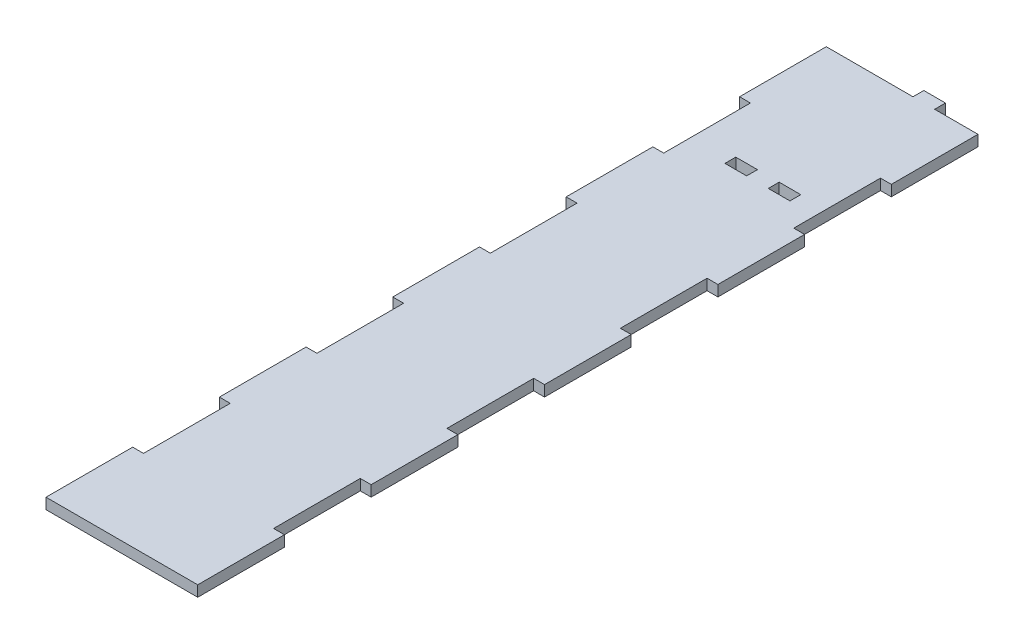
SolidWorks part; units mm, degrees
material "Pine"
ref_plane "Front Plane" through (0, 0, 0) normal (0, 0, 1) x (1, 0, 0)
ref_plane "Top Plane" through (0, 0, 0) normal (0, 1, 0) x (1, 0, 0)
ref_plane "Right Plane" through (0, 0, 0) normal (1, 0, 0) x (0, 0, -1)
sketch "Sketch1" plane through (0, 0, 0) normal (0, 0, 1) x (1, 0, 0)
  line L1 (38.1, -38.1) -> (-38.1, -38.1) construction
  line L2 (38.1, -38.1) -> (38.1, 38.1) construction
  line L3 (38.1, 38.1) -> (-38.1, 38.1)
  line L4 (-38.1, -38.1) -> (-38.1, 38.1) construction
  line L5 (38.1, -38.1) -> (-38.1, 38.1) construction
  line L6 (38.1, 38.1) -> (-38.1, -38.1) construction
  line L7 (-38.1, 38.1) -> (38.1, 38.1)
  line L8 (-38.1, 38.1) -> (-38.1, 44.45)
  line L9 (-38.1, 44.45) -> (38.1, 44.45)
  line L10 (38.1, 38.1) -> (38.1, 44.45)
  point P0 (0, 0)
  dimension "D1" = 76.2
  dimension "D2" = 6.35
extrude "Base Extrusion" add sketch "Sketch1" along normal blind 457.2 contours L3 L10 L9 L8 region at (0, 41.275, 0)
sketch "Sketch2" plane through (0, 44.45, 0) normal (0, 1, 0) x (1, 0, 0)
  line L0 (-44.45, -406.4) -> (-44.45, -355.6) construction
  line L1 (-38.1, -457.2) -> (-44.45, -457.2)
  line L2 (-38.1, -457.2) -> (-38.1, -406.4)
  line L3 (-38.1, -406.4) -> (-44.45, -406.4)
  line L4 (-44.45, -457.2) -> (-44.45, -406.4)
  line L5 (-44.45, -457.2) -> (-44.45, 0) construction
  line L6 (-44.45, -355.6) -> (-44.45, -304.8) construction
  line L7 (-44.45, -304.8) -> (-44.45, -254) construction
  line L8 (-44.45, -254) -> (-44.45, -203.2) construction
  line L9 (-44.45, -203.2) -> (-44.45, -152.4) construction
  line L10 (-44.45, -152.4) -> (-44.45, -101.6) construction
  line L11 (-44.45, -101.6) -> (-44.45, -50.8) construction
  line L12 (-44.45, -50.8) -> (-44.45, 0) construction
  dimension "D1" = 6.35
extrude "Tab" add sketch "Sketch2" against normal up to surface (6.35 mm away) up to face at (0, 38.1, 228.6)
pattern_linear "LPattern1" count 5 spacing 101.6 along (0, 0, -1) of "Tab"
mirror "Mirror2" about plane through (0, 0, 0) normal (1, 0, 0) of "LPattern1"
sketch "Sketch3" plane through (0, 38.1, 0) normal (0, -1, 0) x (-1, 0, 0)
  line L1 (-23.1736, -82.55) -> (-10.4736, -82.55)
  line L2 (-23.1736, -82.55) -> (-23.1736, -88.9)
  line L3 (-23.1736, -88.9) -> (-10.4736, -88.9)
  line L4 (-10.4736, -82.55) -> (-10.4736, -88.9)
  line L5 (2.2264, -82.55) -> (14.9264, -82.55)
  line L6 (2.2264, -82.55) -> (2.2264, -88.9)
  line L7 (2.2264, -88.9) -> (14.9264, -88.9)
  line L8 (14.9264, -82.55) -> (14.9264, -88.9)
extrude "Cut-Extrude1" cut sketch "Sketch3" against normal through all
sketch "Sketch4" plane through (0, 0, 0) normal (0, 0, -1) x (-1, 0, 0)
  line L0 (44.45, 44.45) -> (-44.45, 44.45) construction
  line L1 (-6.35, 44.45) -> (-19.05, 44.45)
  line L2 (-6.35, 44.45) -> (-6.35, 38.1)
  line L3 (-6.35, 38.1) -> (-19.05, 38.1)
  line L4 (-19.05, 44.45) -> (-19.05, 38.1)
  line L5 (-44.45, 38.1) -> (44.45, 38.1) construction
  dimension "D1" = 25.4
  dimension "D2" = 12.7
extrude "Boss-Extrude1" add sketch "Sketch4" along normal blind 6.35
